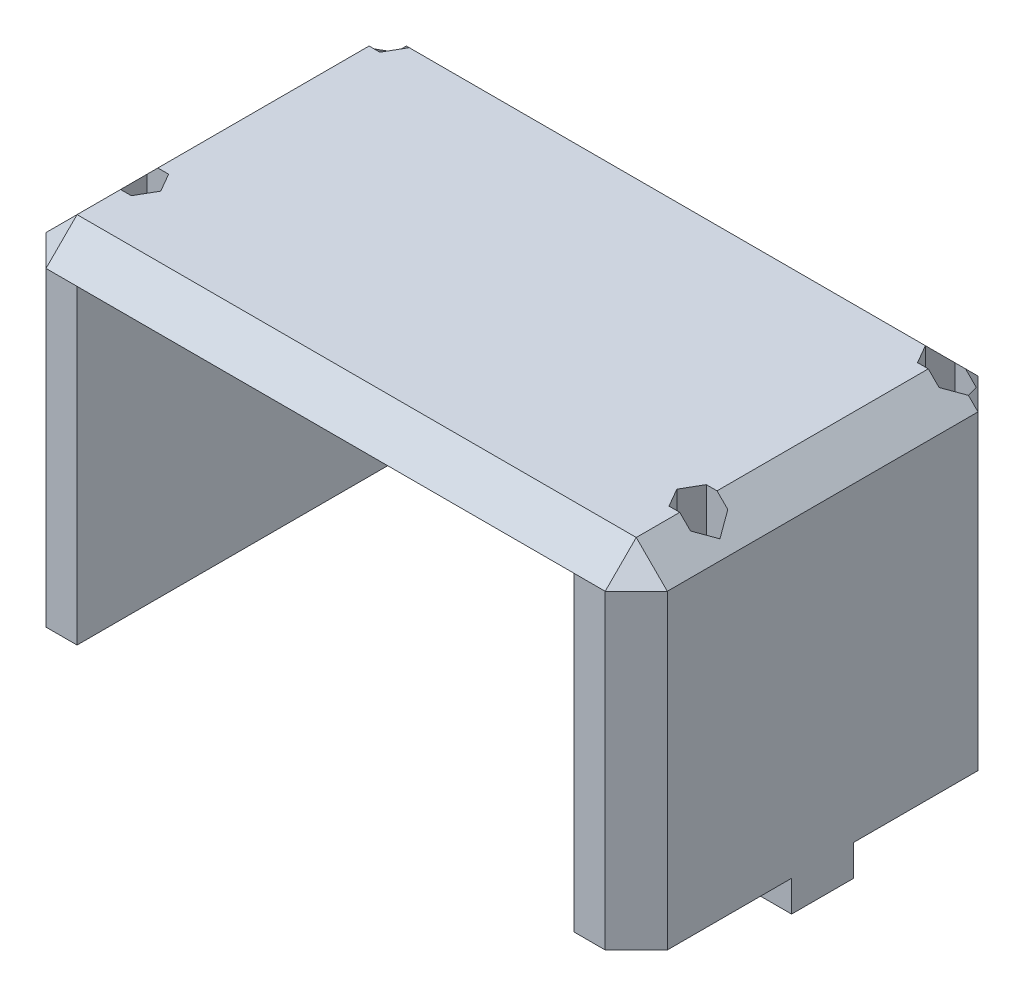
SolidWorks part; units mm, degrees
ref_plane "Płaszczyzna przednia" through (0, 0, 0) normal (0, 0, 1) x (1, 0, 0)
ref_plane "Płaszczyzna górna" through (0, 0, 0) normal (0, 1, 0) x (1, 0, 0)
ref_plane "Płaszczyzna prawa" through (0, 0, 0) normal (1, 0, 0) x (0, 0, -1)
sketch "Sketch1" plane through (0, 0, 0) normal (0, 1, 0) x (1, 0, 0)
  line L1 (-50, -30) -> (50, -30)
  line L2 (-50, -30) -> (-50, 30)
  line L3 (-50, 30) -> (50, 30)
  line L4 (50, -30) -> (50, 30)
  line L5 (-50, -30) -> (50, 30) construction
  line L6 (-50, 30) -> (50, -30) construction
  point P0 (0, 0)
  dimension "D1" = 60
  dimension "D2" = 100
extrude "Boss-Extrude1" add sketch "Sketch1" along normal blind 55
sketch "Sketch2" plane through (0, 0, 0) normal (0, 0, 1) x (1, 0, 0)
  line L0 (-50, 0) -> (50, 0) construction
  line L1 (-40, 0) -> (40, 0)
  line L2 (-40, 0) -> (-40, 50)
  line L3 (-40, 50) -> (40, 50)
  line L4 (40, 0) -> (40, 50)
  line L5 (-50, 55) -> (-50, 0) construction
  line L6 (-50, 55) -> (50, 55) construction
  line L7 (50, 55) -> (50, 0) construction
  dimension "D1" = 10
  dimension "D2" = 5
  dimension "D3" = 10
extrude "Cut-Extrude1" cut sketch "Sketch2" against normal blind 50 from surface starting at face at (0, 27.5, 30)
chamfer "Chamfer2" distance 5 angle 45 8 edges at (0, 55, 30) (-50, 27.5, 30) (-50, 55, 0) (-50, 27.5, -30) (0, 55, -30) (50, 27.5, -30) (50, 55, 0) (50, 27.5, 30)
sketch "Sketch3" plane through (0, 0, 0) normal (0, 1, 0) x (1, 0, 0)
  line L0 (-50, -30) -> (50, -30) construction
  line L1 (-45, -15) -> (45, -15) construction
  line L2 (-45, -15) -> (-45, 25) construction
  line L3 (-45, 25) -> (45, 25) construction
  line L4 (45, -15) -> (45, 25) construction
  line L5 (-45, -15) -> (45, 25) construction
  line L6 (-45, 25) -> (45, -15) construction
  line L7 (50, 30) -> (-50, 30) construction
  line L8 (50, -30) -> (50, 30) construction
  line L10 (-50, 30) -> (-50, -30) construction
  circle A0 centre (-45, 25) radius 1.75
  circle A1 centre (45, 25) radius 1.75
  circle A2 centre (45, -15) radius 1.75
  circle A3 centre (-45, -15) radius 1.75
  point P0 (0, 0)
  dimension "D5" = 3.5
  dimension "D1" = 15
  dimension "D2" = 5
  dimension "D3" = 5
  dimension "D4" = 5
extrude "Cut-Extrude2" cut sketch "Sketch3" along normal through all both and the other way through all
sketch "Sketch4" plane through (0, 0, 0) normal (0, 1, 0) x (1, 0, 0)
  line L1 (-41.5359, 25) -> (-43.2679, 28)
  line L2 (-43.2679, 28) -> (-46.7321, 28)
  line L3 (-46.7321, 28) -> (-48.4641, 25)
  line L4 (-48.4641, 25) -> (-46.7321, 22)
  line L5 (-46.7321, 22) -> (-43.2679, 22)
  line L6 (-43.2679, 22) -> (-41.5359, 25)
  line L7 (-41.5359, -15) -> (-43.2679, -12)
  line L8 (-43.2679, -12) -> (-46.7321, -12)
  line L9 (-46.7321, -12) -> (-48.4641, -15)
  line L10 (-48.4641, -15) -> (-46.7321, -18)
  line L11 (-46.7321, -18) -> (-43.2679, -18)
  line L12 (-43.2679, -18) -> (-41.5359, -15)
  line L13 (48.4641, 25) -> (46.7321, 28)
  line L14 (46.7321, 28) -> (43.2679, 28)
  line L15 (43.2679, 28) -> (41.5359, 25)
  line L16 (41.5359, 25) -> (43.2679, 22)
  line L17 (43.2679, 22) -> (46.7321, 22)
  line L18 (46.7321, 22) -> (48.4641, 25)
  line L19 (48.4641, -15) -> (46.7321, -12)
  line L20 (46.7321, -12) -> (43.2679, -12)
  line L21 (43.2679, -12) -> (41.5359, -15)
  line L22 (41.5359, -15) -> (43.2679, -18)
  line L23 (43.2679, -18) -> (46.7321, -18)
  line L24 (46.7321, -18) -> (48.4641, -15)
  circle A0 centre (-45, 25) radius 3 construction
  circle A1 centre (-45, -15) radius 3 construction
  circle A2 centre (45, 25) radius 3 construction
  circle A3 centre (45, -15) radius 3 construction
  dimension "D1" = 6
  dimension "D2" = 6
  dimension "D3" = 6
  dimension "D4" = 6
extrude "Cut-Extrude3" cut sketch "Sketch4" against normal blind 50 from surface starting at face at (0, 55, 1.4225)
sketch "Sketch5" plane through (0, 0, 0) normal (1, 0, 0) x (0, 0, -1)
  line L0 (5, 0) -> (-5, 0)
  line L1 (5, 0) -> (5, -5)
  line L2 (-5, 0) -> (-5, -5)
  line L3 (5, -5) -> (-5, -5)
  line L4 (25, 0) -> (-25, 0) construction
  line L5 (30, 55) -> (30, 0) construction
  dimension "D1" = 5
  dimension "D2" = 10
  dimension "D3" = 25
extrude "Boss-Extrude2" add sketch "Sketch5" along normal blind 5 from surface starting at face at (-50, 25, 0)
extrude "Boss-Extrude3" add sketch "Sketch5<2>" against normal blind 5 from surface starting at face at (50, 25, 0)
sketch "Sketch5<2>" plane through (0, 0, 0) normal (1, 0, 0) x (0, 0, -1) same geometry as "Sketch5"
sketch "Sketch7" plane through (0, 0, 0) normal (0, 0, 1) x (1, 0, 0)
  line L0 (5, 0) -> (-5, 0)
  line L1 (5, 0) -> (5, -5)
  line L2 (-5, 0) -> (-5, -5)
  line L3 (5, -5) -> (-5, -5)
  line L4 (45, 0) -> (-45, 0) construction
  dimension "D1" = 5
  dimension "D2" = 10
  dimension "D3" = 5
extrude "Boss-Extrude4" add sketch "Sketch7" along normal blind 5 from surface starting at face at (0, 25, -30)
